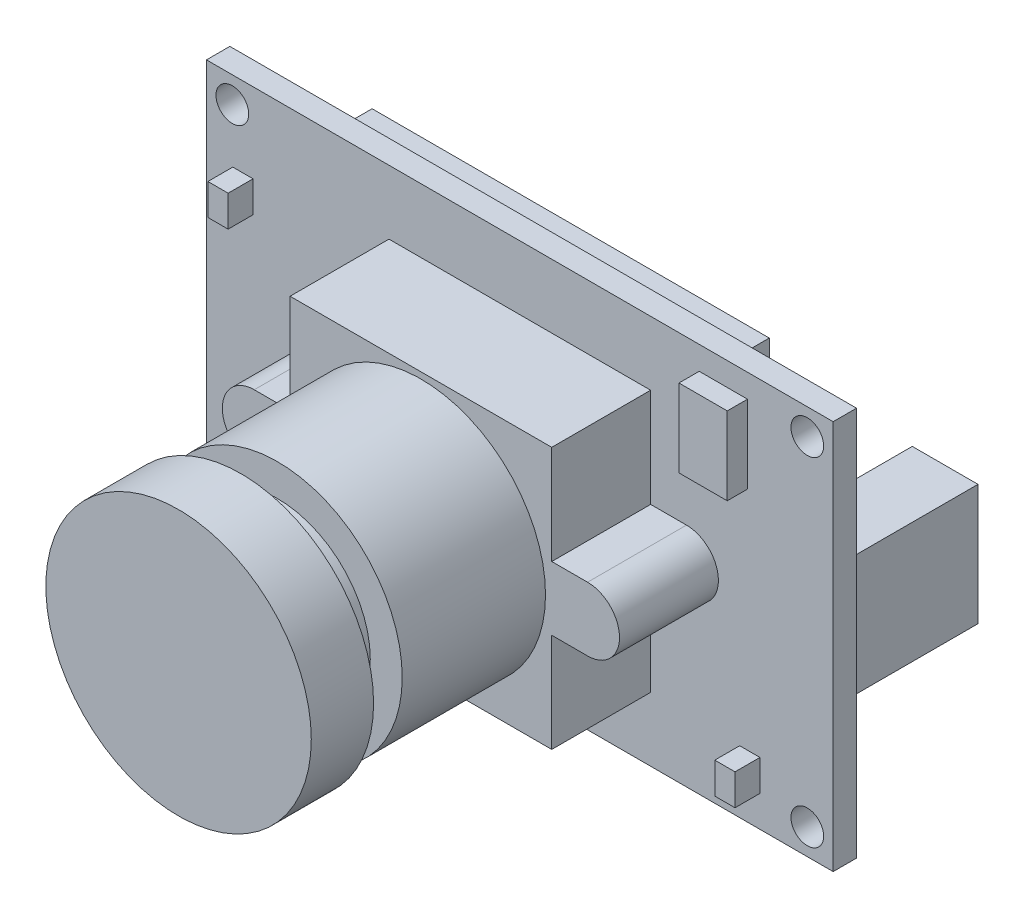
SolidWorks part; units mm, degrees
material "Camera"
ref_plane "Front Plane" through (0, 0, 0) normal (0, 0, 1) x (1, 0, 0)
ref_plane "Top Plane" through (0, 0, 0) normal (0, 1, 0) x (1, 0, 0)
ref_plane "Right Plane" through (0, 0, 0) normal (1, 0, 0) x (0, 0, -1)
sketch "Sketch2" plane through (0, 0, 0) normal (0, 0, 1) x (1, 0, 0)
  line L0 (0, 0) -> (0, 6.003) construction
  line L1 (20.1168, 12.5095) -> (-20.1168, 12.5095)
  line L2 (20.1168, 12.5095) -> (20.1168, -12.5095)
  line L3 (20.1168, -12.5095) -> (-20.1168, -12.5095)
  line L4 (-20.1168, 12.5095) -> (-20.1168, -12.5095)
  line L5 (20.1168, 12.5095) -> (-20.1168, -12.5095) construction
  line L6 (20.1168, -12.5095) -> (-20.1168, 12.5095) construction
  line L7 (-1000, 0) -> (49000, 0) construction
  circle A0 centre (-18.4568, 10.8495) radius 1.05
  circle A1 centre (-18.4568, -10.8495) radius 1.05
  circle A2 centre (18.4568, -10.8495) radius 1.05
  circle A3 centre (18.4568, 10.8495) radius 1.05
  point P0 (0, 0)
  dimension "D5" = 2.1
  dimension "D1" = 40.2336
  dimension "D2" = 25.019
  dimension "D3" = 1.66
  dimension "D4" = 1.66
extrude "Boss-Extrude1" add sketch "Sketch2" along normal blind 1.5
sketch "Sketch3" plane through (0, 0, 1.5) normal (0, 0, 1) x (1, 0, 0)
  line L0 (-8.4, -2.05) -> (-8.4, -8.4)
  line L1 (8.4, 8.4) -> (-8.4, 8.4)
  line L2 (8.4, 8.4) -> (8.4, 2.05)
  line L3 (8.4, -8.4) -> (-8.4, -8.4)
  line L4 (-8.4, 8.4) -> (-8.4, 2.05)
  line L5 (8.4, 8.4) -> (-8.4, -8.4) construction
  line L6 (8.4, -8.4) -> (-8.4, 8.4) construction
  line L7 (-10.7, 2.05) -> (-8.4, 2.05)
  line L8 (0, -1000) -> (0, 49000) construction
  line L9 (-10.7, -2.05) -> (-8.4, -2.05)
  line L10 (10.7, 2.05) -> (8.4, 2.05)
  line L11 (10.7, -2.05) -> (8.4, -2.05)
  line L12 (8.4, -2.05) -> (8.4, -8.4)
  line L13 (-1000, 0) -> (49000, 0) construction
  arc A0 (-10.7, 2.05) -> (-10.7, -2.05) centre (-10.7, 0) ccw
  arc A1 (10.7, 2.05) -> (10.7, -2.05) centre (10.7, 0) cw
  point P0 (0, 0)
  dimension "D1" = 16.8
  dimension "D2" = 16.8
  dimension "D3" = 4.1
  dimension "D4" = 2.3
extrude "Boss-Extrude2" add sketch "Sketch3" along normal blind 6.35
sketch "Sketch4" plane through (0, 0, 7.85) normal (0, 0, 1) x (1, 0, 0)
  circle A0 centre (0, 0) radius 8
  dimension "D1" = 16
extrude "Boss-Extrude3" add sketch "Sketch4" along normal blind 9.2
sketch "Sketch5" plane through (0, 0, 17.05) normal (0, 0, 1) x (1, 0, 0)
  circle A0 centre (0, 0) radius 5.95
  dimension "D1" = 11.9
extrude "Boss-Extrude4" add sketch "Sketch5" along normal blind 2.36
sketch "Sketch6" plane through (0, 0, 19.41) normal (0, 0, 1) x (1, 0, 0)
  circle A0 centre (0, 0) radius 8.5217
  dimension "D1" = 17.0434
extrude "Lens" add sketch "Sketch6" along normal blind 4
sketch "Sketch7" plane through (0, 0, 0) normal (0, 0, -1) x (-1, 0, 0)
  line L0 (0, 0) -> (-20.1168, 0) construction
  line L1 (-15.3968, -3.875) -> (-19.6168, -3.875)
  line L2 (-15.3968, -3.875) -> (-15.3968, 3.875)
  line L3 (-15.3968, 3.875) -> (-19.6168, 3.875)
  line L4 (-19.6168, -3.875) -> (-19.6168, 3.875)
  line L5 (-20.1168, -12.5095) -> (-20.1168, 12.5095) construction
  point P9 (-19.6168, 0)
  dimension "D1" = 7.75
  dimension "D2" = 4.22
  dimension "D3" = 0.5
extrude "Boss-Extrude6" add sketch "Sketch7" along normal blind 8.3
sketch "Sketch8" plane through (0, 0, 0) normal (0, 0, -1) x (-1, 0, 0)
  line L0 (20.1168, 12.5095) -> (20.1168, -12.5095) construction
  line L1 (15.6768, -10.9347) -> (6.6768, -10.9347)
  line L2 (15.6768, -10.9347) -> (15.6768, -7.9488)
  line L3 (15.6768, -7.9488) -> (6.6768, -7.9488)
  line L4 (6.6768, -10.9347) -> (6.6768, -7.9488)
  line L5 (20.1168, -12.5095) -> (-20.1168, -12.5095) construction
  dimension "D1" = 4.44
  dimension "D2" = 1.5748
  dimension "D3" = 9
  dimension "D4" = 2.9859
extrude "Boss-Extrude7" add sketch "Sketch8" along normal blind 4.35
sketch "Sketch9" plane through (0, 0, 1.5) normal (0, 0, 1) x (1, 0, 0)
  line L0 (20.1168, -12.5095) -> (20.1168, 12.5095) construction
  line L1 (11.5168, 11.0095) -> (14.6168, 11.0095)
  line L2 (11.5168, 11.0095) -> (11.5168, 6.0095)
  line L3 (11.5168, 6.0095) -> (14.6168, 6.0095)
  line L4 (14.6168, 11.0095) -> (14.6168, 6.0095)
  line L5 (20.1168, 12.5095) -> (-20.1168, 12.5095) construction
  dimension "D1" = 3.1
  dimension "D2" = 5
  dimension "D3" = 5.5
  dimension "D4" = 1.5
extrude "Boss-Extrude8" add sketch "Sketch9" along normal blind 1.3
sketch "Sketch10" plane through (0, 0, 0) normal (0, 0, -1) x (-1, 0, 0)
  line L0 (-20.1168, -12.5095) -> (-20.1168, 12.5095) construction
  line L1 (-13.1168, 12.2095) -> (12.3832, 12.2095)
  line L2 (-13.1168, 12.2095) -> (-13.1168, 4.2095)
  line L3 (-13.1168, 4.2095) -> (12.3832, 4.2095)
  line L4 (12.3832, 12.2095) -> (12.3832, 4.2095)
  line L5 (-13.1168, 12.2095) -> (12.3832, 4.2095) construction
  line L6 (-13.1168, 4.2095) -> (12.3832, 12.2095) construction
  line L7 (-20.1168, 12.5095) -> (20.1168, 12.5095) construction
  point P0 (-0.3668, 8.2095)
  dimension "D1" = 25.5
  dimension "D2" = 8
  dimension "D3" = 7
  dimension "D4" = 0.3
extrude "Boss-Extrude9" add sketch "Sketch10" along normal blind 1.4
sketch "Sketch11" plane through (0, 0, 1.5) normal (0, 0, 1) x (1, 0, 0)
  line L0 (20.1168, -12.5095) -> (20.1168, 12.5095) construction
  line L1 (15.4168, -10.5095) -> (14.1168, -10.5095)
  line L2 (15.4168, -10.5095) -> (15.4168, -8.5095)
  line L3 (15.4168, -8.5095) -> (14.1168, -8.5095)
  line L4 (14.1168, -10.5095) -> (14.1168, -8.5095)
  line L5 (-20.1168, -12.5095) -> (20.1168, -12.5095) construction
  line L6 (-17.1271, 5.3916) -> (-18.4271, 5.3916)
  line L7 (-17.1271, 5.3916) -> (-17.1271, 7.3916)
  line L8 (-17.1271, 7.3916) -> (-18.4271, 7.3916)
  line L9 (-18.4271, 5.3916) -> (-18.4271, 7.3916)
  dimension "D1" = 1.3
  dimension "D2" = 2
  dimension "D3" = 6
  dimension "D4" = 2
extrude "Boss-Extrude10" add sketch "Sketch11" along normal blind 1.6
sketch "Sketch12" plane through (0, 0, 0) normal (0, 0, -1) x (-1, 0, 0)
  line L0 (-20.1168, 12.5095) -> (20.1168, 12.5095) construction
  line L1 (19.1168, 5.1095) -> (16.1168, 5.1095)
  line L2 (19.1168, 5.1095) -> (19.1168, 8.1095)
  line L3 (19.1168, 8.1095) -> (16.1168, 8.1095)
  line L4 (16.1168, 5.1095) -> (16.1168, 8.1095)
  line L5 (20.1168, 12.5095) -> (20.1168, -12.5095) construction
  dimension "D1" = 3
  dimension "D2" = 3
  dimension "D3" = 7.4
  dimension "D4" = 1
extrude "Boss-Extrude11" add sketch "Sketch12" along normal blind 1.4
sketch "Sketch13" plane through (0, 0, 0) normal (0, 0, -1) x (-1, 0, 0)
  line L0 (-20.1168, -12.5095) -> (-20.1168, 12.5095) construction
  line L1 (-14.1478, -9.3853) -> (-10.9728, -9.3853)
  line L2 (-14.1478, -9.3853) -> (-14.1478, -12.0015)
  line L3 (-14.1478, -12.0015) -> (-10.9728, -12.0015)
  line L4 (-10.9728, -9.3853) -> (-10.9728, -12.0015)
  line L5 (20.1168, -12.5095) -> (-20.1168, -12.5095) construction
  line L7 (-7.1628, -7.1755) -> (1.3462, -7.1755)
  line L8 (-7.1628, -7.1755) -> (-7.1628, -12.0015)
  line L9 (-7.1628, -12.0015) -> (1.3462, -12.0015)
  line L10 (1.3462, -7.1755) -> (1.3462, -12.0015)
  dimension "D1" = 3.175
  dimension "D2" = 2.6162
  dimension "D3" = 5.969
  dimension "D4" = 0.508
  dimension "D5" = 8.509
  dimension "D6" = 4.826
  dimension "D7" = 12.954
  dimension "D8" = 0.508
extrude "Boss-Extrude12" add sketch "Sketch13" along normal blind 2.7432
